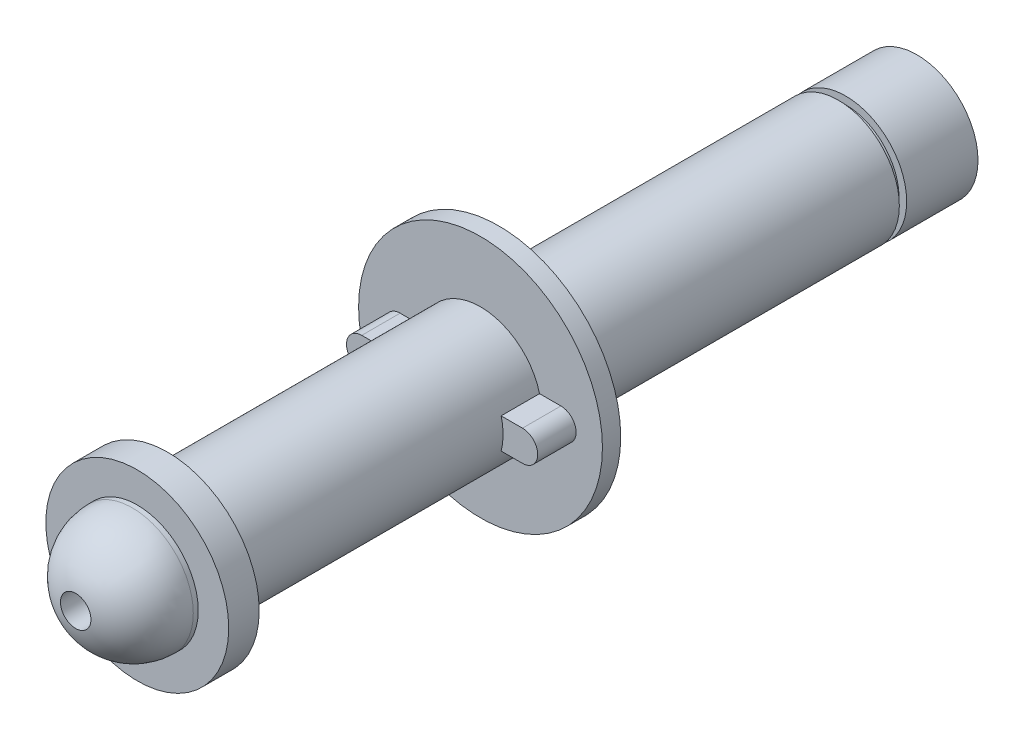
SolidWorks part; units mm, degrees
ref_plane "Front Plane" through (0, 0, 0) normal (0, 0, 1) x (1, 0, 0)
ref_plane "Top Plane" through (0, 0, 0) normal (0, 1, 0) x (1, 0, 0)
ref_plane "Right Plane" through (0, 0, 0) normal (1, 0, 0) x (0, 0, -1)
sketch "Sketch1" plane through (0, 0, 0) normal (0, 0, 1) x (1, 0, 0)
  circle A0 centre (0, 0) radius 20
  circle A1 centre (0, 0) radius 5
  dimension "D1" = 40
  dimension "D2" = 10
extrude "Boss-Extrude1" add sketch "Sketch1" along normal blind 166
sketch "Esquisse3" plane through (0, 0, 166) normal (0, 0, 1) x (1, 0, 0)
  circle A0 centre (0, 0) radius 17.5
  circle A2 centre (0, 0) radius 20
  circle A3 centre (0, 0) radius 20
  dimension "D1" = 35
  dimension "D2" = 0
extrude "Enlèv. mat.-Extru.1" cut sketch "Esquisse3" against normal blind 2.4 from offset 140.2 offset against normal yes
sketch "Esquisse4" plane through (0, 0, 166) normal (0, 0, 1) x (1, 0, 0)
  circle A0 centre (0, 0) radius 17.5
  circle A2 centre (0, 0) radius 20
  circle A4 centre (0, 0) radius 20
  dimension "D1" = 35
  dimension "D2" = 0
extrude "Enlèv. mat.-Extru.2" cut sketch "Esquisse4" against normal blind 2.4 from offset 29.8 offset against normal yes
sketch "Esquisse5" plane through (0, 0, 166) normal (0, 0, 1) x (1, 0, 0)
  line L0 (12.8896, 0) -> (-19.3344, 0) construction
  line L3 (-19.3649, 5) -> (-26.3649, 5)
  line L4 (-19.3649, -5) -> (-26.3649, -5)
  line L5 (0, 12.4197) -> (0, -17.5135) construction
  line L6 (19.3649, -5) -> (26.3649, -5)
  line L7 (19.3649, 5) -> (26.3649, 5)
  circle A2 centre (0, 0) radius 20 construction
  arc A3 (-26.3649, 5) -> (-26.3649, -5) centre (-26.3649, 0) ccw
  arc A4 (26.3649, 5) -> (26.3649, -5) centre (26.3649, 0) cw
  arc A5 (-19.3649, -5) -> (-19.3649, 5) centre (0, 0) cw
  arc A6 (19.3649, -5) -> (19.3649, 5) centre (0, 0) ccw
  dimension "D1" = 7
  dimension "D2" = 5
extrude "Boss.-Extru.1" add sketch "Esquisse5" along normal blind 12.6 from offset 22.8 offset against normal yes
sketch "Esquisse6" plane through (0, 0, 166) normal (0, 0, 1) x (1, 0, 0)
  circle A0 centre (0, 0) radius 20
  circle A1 centre (0, 0) radius 5
  circle A3 centre (0, 0) radius 20
  circle A4 centre (0, 0) radius 20
  circle M3 centre (0, 0) radius 20
  circle M4 centre (0, 0) radius 5
  dimension "D2" = 40
  dimension "D1" = 0
extrude "Boss.-Extru.2" add sketch "Esquisse6" along normal blind 110 contours M3 M4
sketch "Esquisse7" plane through (0, 0, 276) normal (0, 0, 1) x (1, 0, 0)
  circle A0 centre (0, 0) radius 40
  dimension "D1" = 80
extrude "Boss.-Extru.3" add sketch "Esquisse7" against normal blind 6 from offset 132.8 offset against normal yes
sketch "Esquisse8" plane through (0, 0, 276) normal (0, 0, 1) x (1, 0, 0)
  circle A0 centre (0, 0) radius 30
  dimension "D1" = 60
extrude "Boss.-Extru.4" add sketch "Esquisse8" along normal blind 10 from offset 30.2 offset against normal yes
fillet "Congé3" radius 19 1 edges at (20, 0, 276)
scale "Echelle1" scale about centroid uniform scaling yes scale factor 0.25
